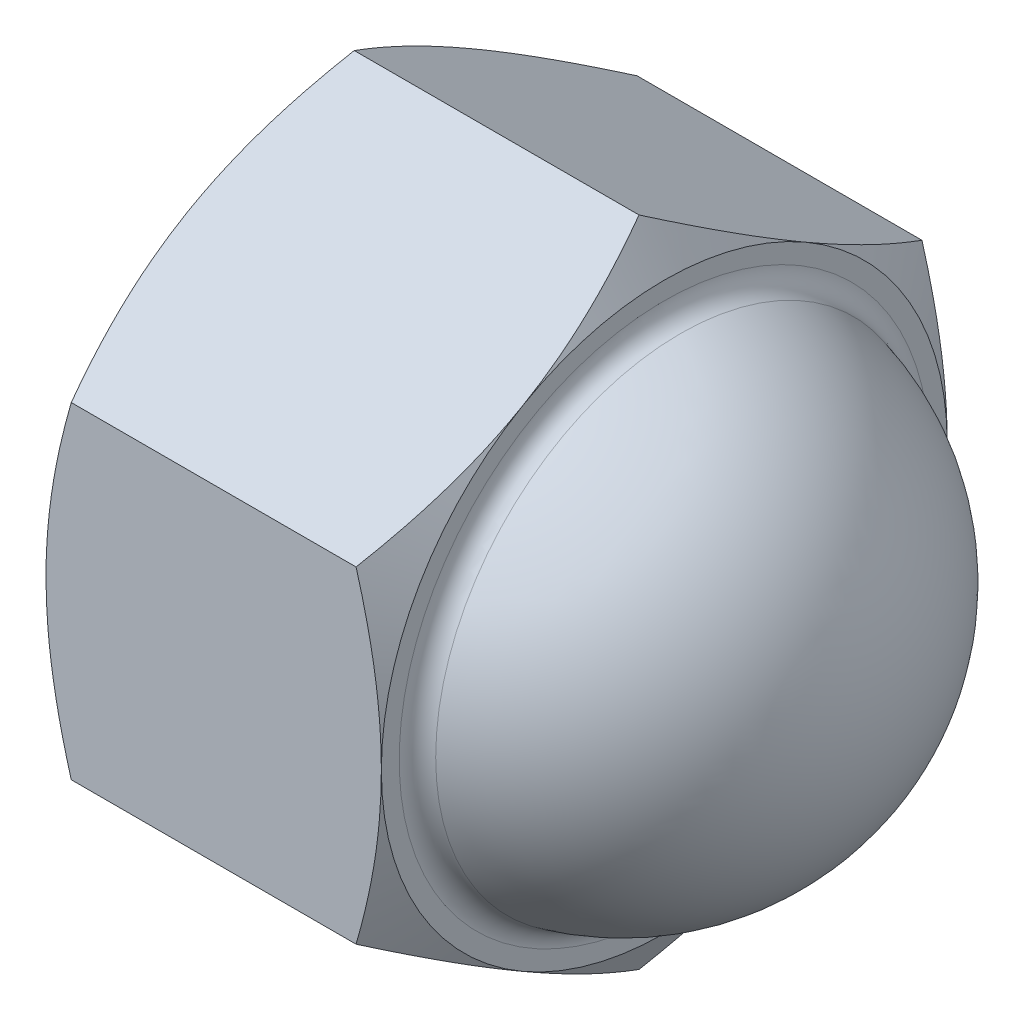
SolidWorks part; units mm, degrees
extrude "BaseNut" add sketch "BaseNutSke" along normal blind 16
sketch "BaseNutSke" plane through (0, 0, 0) normal (1, 0, 0) x (0, 0, -1)
  line L6 (13.5, 7.7942) -> (13.5, -7.7942)
  line L7 (-13.5, 7.7942) -> (-13.5, -7.7942)
  line L8 (13.5, 7.7942) -> (0, 15.5885)
  line L9 (0, 15.5885) -> (-13.5, 7.7942)
  line L10 (-13.5, -7.7942) -> (0, -15.5885)
  line L11 (0, -15.5885) -> (13.5, -7.7942)
  dimension "D4" = 60
  dimension "D1" = 120
  dimension "D2" = 13.5
  dimension "D3" = 13.5
  dimension "Width_flats" = 27
revolve "DoubleChamfer" cut sketch "Sketch4" angle 360 about L10 other way angle 118
sketch "Sketch4" plane through (0, 0, 0) normal (0, 0, 1) x (1, 0, 0)
  line L0 (0, 13.5) -> (2.5048, 17.8385)
  line L1 (16, 13.5) -> (13.4952, 17.8385)
  line L2 (2.5048, 17.8385) -> (13.4952, 17.8385)
  line L3 (16, 13.5) -> (18, 13.5)
  line L4 (18, 13.5) -> (18, 28.5)
  line L5 (18, 28.5) -> (-2, 28.5)
  line L6 (0, 13.5) -> (-2, 13.5)
  line L7 (-2, 13.5) -> (-2, 28.5)
  line L8 (16, 15.5885) -> (16, 7.7942) construction
  line L9 (0, 15.5885) -> (0, 7.7942) construction
  line L10 (0, 0) -> (57.15, 0) construction
  line L11 (16, 15.5885) -> (0, 15.5885) construction
  point P17 (16, 13.5)
  dimension "D1" = 30
  dimension "D2" = 30
  dimension "D3" = 2
  dimension "D4" = 2
  dimension "D5" = 2.25
  dimension "D6" = 15
  dimension "D7" = 13.5
ref_plane "Plane1" through (0, 0, 0) normal (0, 0, 1) x (1, 0, 0)
ref_plane "Plane2" through (0, 0, 0) normal (0, 1, 0) x (1, 0, 0)
ref_plane "Plane3" through (0, 0, 0) normal (1, 0, 0) x (0, 0, -1)
sketch "DomeSke" plane through (0, 0, 0) normal (0, 0, 1) x (1, 0, 0)
  line L0 (0, 0) -> (63.5, 0) construction
  line L2 (26, 0) -> (24.4, 0)
  line L3 (0, 12) -> (14, 12)
  line L5 (0, 12) -> (0, 10.4)
  line L8 (0, 10.4) -> (14, 10.4)
  arc A0 (14, 12) -> (26, 0) centre (14, 0) cw
  arc A1 (14, 10.4) -> (24.4, 0) centre (14, 0) cw
  dimension "Dome_thk" = 1.6
revolve "Dome" add sketch "DomeSke" angle 360 about L0
sketch "TapDriSke" plane through (0, 0, 0) normal (0, 0, 1) x (1, 0, 0)
  line L0 (0, 0) -> (44.45, 0) construction
  line L1 (0, 8.75) -> (18.4, 8.75)
  line L2 (0, 0) -> (0, -11.6913) construction
  line L3 (18.4, 8.75) -> (23.6575, 0)
  line L4 (0, 0) -> (63.5, 0) construction
  line L5 (23.6575, 0) -> (0, 0)
  line L6 (0, 0) -> (0, 8.75)
  line L7 (18.4, -8.75) -> (23.6575, 0) construction
  line L8 (0, -8.75) -> (18.4, -8.75) construction
  line L9 (0.5, 6.35) -> (0.5, 3.175) construction
  dimension "Drill_depth" = 18.4
revolve "TapDrill" cut sketch "TapDriSke"
cosmetic thread "ThreadCosmetic" [suppressed]
revolve "EndChamfer" cut sketch "EndChamferSketch" angle 360 about L4
sketch "EndChamferSketch" plane through (0, 0, 0) normal (0, 0, 1) x (1, 0, 0)
  line L0 (-0.0746, 10) -> (0.0254, 10)
  line L1 (0.0254, 10) -> (0.9882, 8.625)
  line L2 (0.9882, 8.625) -> (-0.0746, 8.625)
  line L3 (-0.0746, 8.625) -> (-0.0746, 10)
  line L4 (0, 0) -> (-15.875, 0) construction
  line L5 (15.9746, 10) -> (16.1, 10)
  line L6 (16.1, 10) -> (16.1, 8.625)
  line L7 (16.1, 8.625) -> (15.0118, 8.625)
  line L8 (15.0118, 8.625) -> (15.9746, 10)
  line L9 (16, -11.6913) -> (16, 0) construction
  dimension "D1" = 0.1
  dimension "D2" = 35
  dimension "ChamferDepth" = 1.375
  dimension "D3" = 0.0254
  dimension "D4" = 35
  dimension "D5" = 0.1
  dimension "D6" = 0.0254
sketch "ThdSchSke" plane through (0, 0, 0) normal (0, 1, 0) x (1, 0, 0)
  line L0 (0.0381, 10) -> (-0.8372, 8.75)
  line L1 (-0.8372, 8.75) -> (-0.8372, 4.375)
  line L2 (-0.8372, 4.375) -> (0.9134, 4.375)
  line L3 (0.9134, 4.375) -> (0.9134, 8.75)
  line L4 (0.9134, 8.75) -> (0.0381, 10)
  line L5 (-38.1, 0) -> (3.175, 0) construction
  line L6 (0, 0) -> (-15.875, 0) construction
  line L7 (0, 0) -> (63.5, 0) construction
  line L9 (2.5381, 0.475) -> (2.5381, -5.875) construction
  dimension "D1" = 0.0381
  dimension "Thread_major" = 20
  dimension "Tap_drill" = 17.5
  dimension "OverCut" = 8.75
revolve "ThreadSchematic" [suppressed] cut sketch "ThdSchSke" angle 360 about L5
pattern_linear "ThdSchPat" [suppressed]
fillet "DomeFillet" radius 1 1 edges at (16, 0, -11.8322)
equation "' \"Width_flats@BaseNutSke\" = 27"
equation "' \"Hex_ht@BaseNut\" = 16"
equation "' \"Overall_ht@DomeSke\" = 26"
equation "' \"Dome_rad@DomeSke\" = 12"
equation "' \"Thread_min@TapDriSke\" = 17.5"
equation "' \"Drill_clr@TapDriSke\" = 1.0"
equation "' \"Advance@ThdSchSke\" = 2.5"
equation "' \"Thread_nominal@ThreadCosmetic\" = 20"
equation "' \"Radius@DomeFillet\" = 1.0"
equation "' \"Dome_thk@DomeSke\" = 1.6"
equation "\"Drill_depth@TapDriSke\" = \"Overall_ht@DomeSke\"  - \"Dome_thk@DomeSke\"- 0.3 * \"Thread_nominal@ThreadCosmetic\""
equation "\"Thread_depth@ThreadCosmetic\" = \"Thread_nominal@ThreadCosmetic\""
equation "\"D2@BaseNutSke\" = \"Width_flats@BaseNutSke\" / 2"
equation "\"D3@BaseNutSke\" = \"Width_flats@BaseNutSke\" / 2"
equation "\"D7@Sketch4\" = \"Width_flats@BaseNutSke\" / 2"
equation "\"D5@Sketch4\" = \"Width_flats@BaseNutSke\" / 12"
equation "\"Thread_major@ThdSchSke\" = \"Thread_nominal@ThreadCosmetic\""
equation "\"Tap_drill@ThdSchSke\" = \"Thread_min@TapDriSke\""
equation "\"OverCut@ThdSchSke\" = \"Tap_drill@ThdSchSke\" * 0.5"
equation "\"Num_threads@ThdSchPat\" = int(  ( \"Hex_ht@BaseNut\" - 0.002 ) / \"Advance@ThdSchSke\" + 0.999 )  + 1"
equation "' \"Num_threads@ThdSchPat\" = int(  ( \"Thread_depth@ThreadCosmetic\" - 0.002 ) / \"Advance@ThdSchSke\" + 0.999 )  + 1"
equation "\"Advance@ThdSchPat\" = ( \"Hex_ht@BaseNut\" - 0.002 ) /  (\"Num_threads@ThdSchPat\" - 1) 'relax it"
equation "' \"Advance@ThdSchPat\" = ( \"Thread_depth@ThreadCosmetic\" - 0.002 ) /  (\"Num_threads@ThdSchPat\" - 1) 'relax it"
equation "\"ThreadMajor@EndChamferSketch\" = \"Thread_nominal@ThreadCosmetic\" * 0.5"
equation "\"ChamferDepth@EndChamferSketch\" = (\"Thread_nominal@ThreadCosmetic\" - \"Thread_min@TapDriSke\") * 0.55"
